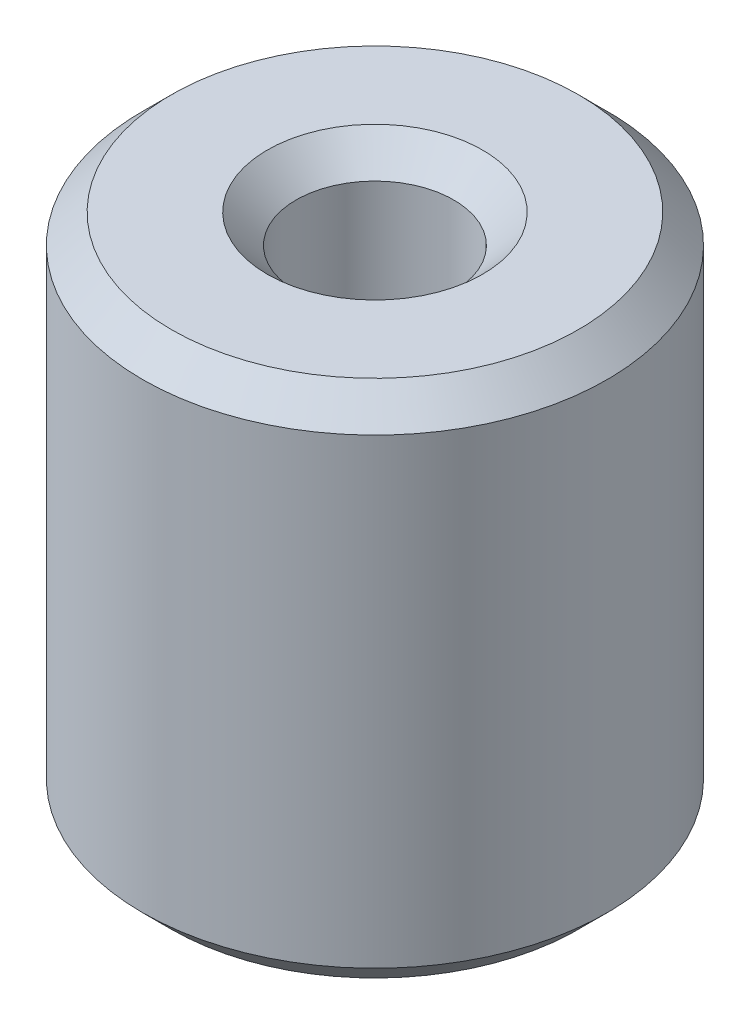
SolidWorks part; units mm, degrees
ref_plane "Front Plane" through (0, 0, 0) normal (0, 0, 1) x (1, 0, 0)
ref_plane "Top Plane" through (0, 0, 0) normal (0, 1, 0) x (1, 0, 0)
ref_plane "Right Plane" through (0, 0, 0) normal (1, 0, 0) x (0, 0, -1)
sketch "Sketch1" plane through (0, 0, 0) normal (0, 1, 0) x (1, 0, 0)
  circle A0 centre (0, 0) radius 5
  dimension "SLEEVE_OD" = 10
extrude "Boss-Extrude1" add sketch "Sketch1" along normal blind 11.1765
sketch "Sketch2" plane through (0, 0, 0) normal (0, 1, 0) x (1, 0, 0)
  circle A0 centre (0, 0) radius 1.6968
  dimension "BORE_D" = 3.3937
extrude "Cut-Extrude1" cut sketch "Sketch2" along normal through all
chamfer "Chamfer1" distance 0.6202 angle 45 4 edges at (0, 11.1765, 1.6968) (0, 0, 1.6968) (0, 0, 5) (0, 11.1765, 5)
